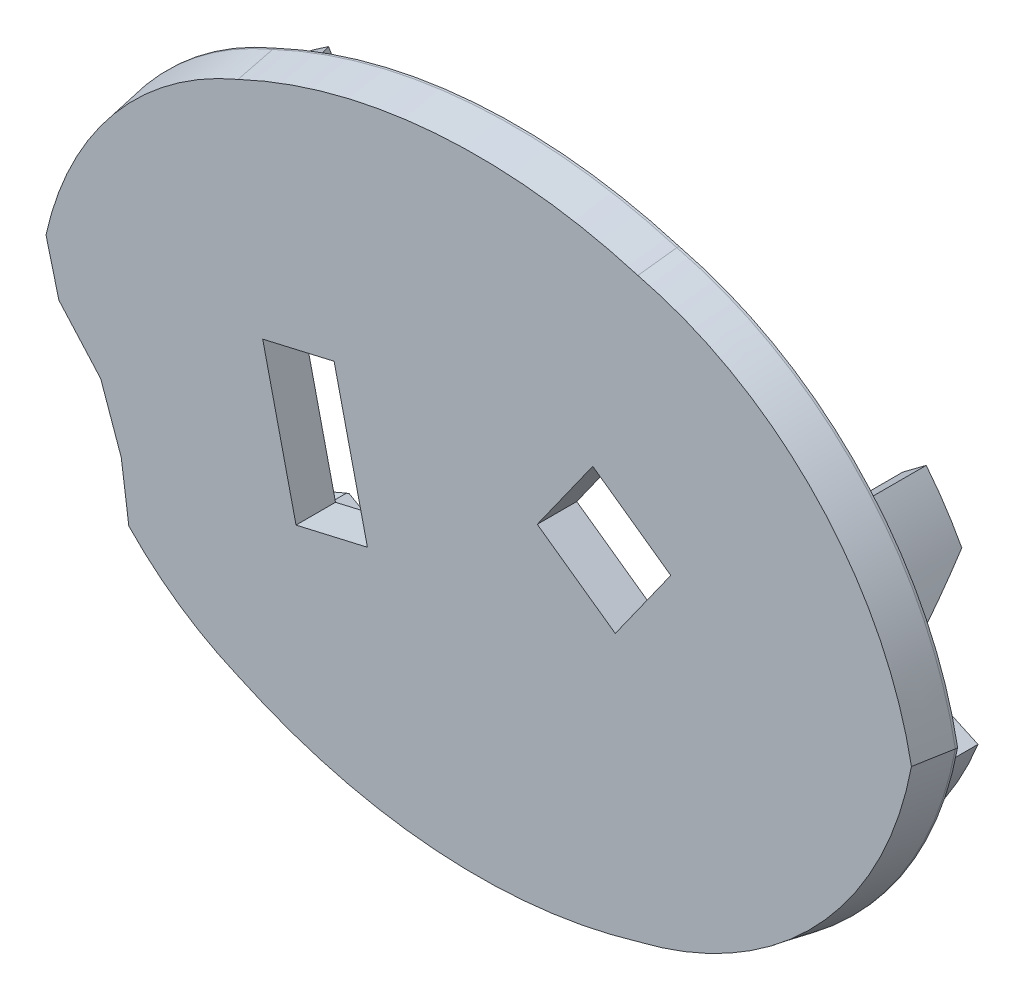
SolidWorks part; units mm, degrees
ref_plane "Ön Düzlem" through (0, 0, 0) normal (0, 0, 1) x (1, 0, 0)
ref_plane "Üst Düzlem" through (0, 0, 0) normal (0, 1, 0) x (1, 0, 0)
ref_plane "Sağ Düzlem" through (0, 0, 0) normal (1, 0, 0) x (0, 0, -1)
sketch "Çizim1" plane through (0, 0, 0) normal (0, 0, 1) x (1, 0, 0)
  line L2 (-58.677, -17.6893) -> (-56.8396, -24.8216)
  line L3 (-56.8396, -24.8216) -> (-51.1973, -31.1692)
  line L8 (-51.1973, -31.1692) -> (-48.5261, -38.7135)
  line L9 (-48.5261, -38.7135) -> (-47.4867, -46.3583)
  arc A1 (59.3086, -21.378) -> (21.9184, 18.1981) centre (10.0775, -30.4393) ccw
  arc A2 (21.9184, 18.1981) -> (-32.3459, 14.1122) centre (0.1322, -54.8435) ccw
  arc A5 (-32.3459, 14.1122) -> (-58.677, -17.6893) centre (-14.9778, -27.0699) ccw
  arc A6 (-32.3459, -56.8682) -> (-47.4867, -46.3583) centre (-14.9778, -15.6861) cw
  arc A9 (21.9184, -60.9541) -> (-32.3459, -56.8682) centre (0.1322, 12.0875) cw
  arc A10 (59.3086, -21.378) -> (21.9184, -60.9541) centre (10.0775, -12.3167) cw
extrude "Yükseklik-Ekstrüzyon1" add sketch "Çizim1" along normal blind 5.3
chamfer "Pah1" distance 5 angle 10 10 edges at (46.4645, 3.9379, 5.3) (46.4645, -46.6939, 5.3) (-5.5908, -63.9188, 5.3) (-40.464, -52.4022, 5.3) (-48.0064, -42.5359, 5.3) (-49.8617, -34.9414, 5.3) (-54.0184, -27.9954, 5.3) (-57.7583, -21.2554, 5.3) (-49.4036, 1.4341, 5.3) (-5.5908, 21.1628, 5.3) first distance on face at (43.539, 1.174, 2.65) first distance on face at (43.539, -43.93, 2.65) first distance on face at (-5.4023, -61.415, 2.65) first distance on face at (-40.1901, -52.0077, 2.65) first distance on face at (-48.0064, -42.5359, 2.65) first distance on face at (-49.8617, -34.9414, 2.65) first distance on face at (-54.0184, -27.9954, 2.65) first distance on face at (-57.7583, -21.2554, 2.65) first distance on face at (-47.4575, -0.1772, 2.65) first distance on face at (-5.4023, 18.659, 2.65)
sketch "Çizim2" plane through (0, 0, 0) normal (0, 0, -1) x (-1, 0, 0)
  line L0 (31.2763, 9.847) -> (27.7371, 3.911)
  line L1 (42.8096, -9.0722) -> (46.8763, -3.3933)
  line L2 (26.6903, -46.7388) -> (31.033, -53.1744)
  line L3 (39.0108, -42.3852) -> (40.3977, -36.6901)
  line L4 (40.3977, -36.6901) -> (43.5033, -30.0469)
  line L5 (43.5033, -30.0469) -> (48.6913, -24.7392)
  line L6 (48.6913, -24.7392) -> (53.3702, -18.2488)
  line L7 (-19.9716, 14.4087) -> (-19.195, 12.4343)
  line L8 (-41.465, -3.5137) -> (-44.5942, -1.1798)
  line L9 (-44.8646, -27.0758) -> (-51.5468, -30.1376)
  line L10 (-32.8861, -43.1983) -> (-38.7588, -48.0169)
  line L11 (-44.8646, -9.307) -> (-41.465, -3.5137)
  line L17 (39.0108, -42.3852) -> (33.018, -43.1064)
  line L18 (33.018, -43.1064) -> (26.6903, -46.7388)
  line L25 (43.1871, -44.3376) -> (39.0108, -42.3852)
  line L27 (-49.8231, -14.3904) -> (-51.9148, -14.0339)
  line L29 (-41.465, -3.5137) -> (-44.8646, -9.307)
  line L30 (9.7339, 13.9491) -> (10.6003, 16.4649)
  line L31 (-4.7237, 14.7755) -> (-4.8826, 17.1405)
  line L32 (-32.8861, -43.1983) -> (-31.6707, -49.9851)
  line L33 (-44.8646, -9.307) -> (-49.8231, -14.3904)
  line L34 (44.1329, -37.3808) -> (43.1871, -44.3376)
  line L35 (46.5637, -30.5155) -> (44.1329, -37.3808)
  line L36 (51.6981, -24.7392) -> (46.5637, -30.5155)
  line L37 (53.3702, -18.2488) -> (51.6981, -24.7392)
  line L38 (-31.6707, -49.9851) -> (-24.6864, -53.5082)
  line L39 (-24.6864, -53.5082) -> (-25.5321, -55.8827)
  arc A0 (27.7371, 3.911) -> (42.8096, -9.0722) centre (19.0626, -21.4001) cw
  arc A1 (-4.7237, 14.7755) -> (9.7339, 13.9491) centre (-0.0333, -30.0469) cw
  arc A2 (-44.8646, -27.0758) -> (-32.8861, -43.1983) centre (-10.3568, -13.9486) ccw
  arc A3 (-19.195, 12.4343) -> (-43.0296, -2.3468) centre (-9.4062, -29.9574) ccw
  arc A16 (-51.5468, -30.1376) -> (-25.5321, -55.8827) centre (-9.1964, -13.3597) ccw
  arc A17 (31.033, -53.1744) -> (43.1871, -44.3376) centre (13.6039, -16.4259) ccw
  arc A19 (46.8763, -3.3933) -> (31.2763, 9.847) centre (13.6039, -26.7852) ccw
  arc A20 (10.6003, 16.4649) -> (-4.8826, 17.1405) centre (-0.1461, -52.0591) ccw
  arc A21 (-19.9716, 14.4087) -> (-51.9148, -14.0339) centre (-9.1964, -29.8513) ccw
extrude "Yükseklik-Ekstrüzyon2" add sketch "Çizim2" along normal blind 10.5 contours L1 A19 L0 A0 | L8 A21 L27 L33 L11 | L9 A16 L10 A2 | L2 A17 L25 L17 L18 region at (-37.7924, 1.217, 0) region at (-34.4304, -46.9883, 0) region at (46.6249, -7.7509, 0) region at (42.7824, -37.6935, 0)
ref_plane "Düzlem1" through (0, 0, -2.5) normal (0, 0, -1) x (-1, 0, 0)
sketch "Çizim4" plane through (0, 0, -2.5) normal (0, 0, -1) x (-1, 0, 0)
  line L0 (-32.8861, -43.1983) -> (-38.7588, -48.0169) construction
  line L1 (-19.9716, 14.4087) -> (-19.195, 12.4343) construction
  line L2 (-49.8231, -14.3904) -> (-51.9148, -14.0339) construction
  line L3 (-44.8646, -9.307) -> (-49.8231, -14.3904) construction
  line L4 (-44.8646, -9.307) -> (-41.465, -3.5137) construction
  line L5 (-41.465, -3.5137) -> (-44.8646, -9.307) construction
  line L6 (-41.465, -3.5137) -> (-44.5942, -1.1798) construction
  line L7 (43.1871, -44.3376) -> (39.0108, -42.3852) construction
  line L8 (31.2763, 9.847) -> (27.7371, 3.911) construction
  line L9 (42.8096, -9.0722) -> (46.8763, -3.3933) construction
  line L10 (39.0108, -42.3852) -> (40.3977, -36.6901) construction
  line L11 (40.3977, -36.6901) -> (43.5033, -30.0469) construction
  line L12 (43.5033, -30.0469) -> (48.6913, -24.7392) construction
  line L13 (48.6913, -24.7392) -> (53.3702, -18.2488) construction
  line L14 (53.3702, -18.2488) -> (51.6981, -24.7392) construction
  line L15 (51.6981, -24.7392) -> (46.5637, -30.5155) construction
  line L16 (46.5637, -30.5155) -> (44.1329, -37.3808) construction
  line L17 (44.1329, -37.3808) -> (43.1871, -44.3376) construction
  line L18 (26.6903, -46.7388) -> (31.033, -53.1744) construction
  line L19 (33.018, -43.1064) -> (26.6903, -46.7388) construction
  line L20 (39.0108, -42.3852) -> (33.018, -43.1064) construction
  line L21 (9.7339, 13.9491) -> (10.6003, 16.4649) construction
  line L22 (-4.7237, 14.7755) -> (-4.8826, 17.1405) construction
  line L23 (-32.8861, -43.1983) -> (-31.6707, -49.9851) construction
  line L24 (-31.6707, -49.9851) -> (-24.6864, -53.5082) construction
  line L25 (-24.6864, -53.5082) -> (-25.5321, -55.8827) construction
  line L26 (-44.8646, -27.0758) -> (-51.5468, -30.1376) construction
  line L27 (-32.8861, -43.1983) -> (-38.7588, -48.0169)
  line L28 (-19.9716, 14.4087) -> (-19.195, 12.4343)
  line L29 (-49.8231, -14.3904) -> (-51.9148, -14.0339)
  line L30 (-44.8646, -9.307) -> (-49.8231, -14.3904)
  line L31 (-44.8646, -9.307) -> (-41.465, -3.5137)
  line L32 (-41.465, -3.5137) -> (-44.8646, -9.307)
  line L33 (-41.465, -3.5137) -> (-44.5942, -1.1798)
  line L34 (43.1871, -44.3376) -> (39.0108, -42.3852)
  line L35 (31.2763, 9.847) -> (27.7371, 3.911)
  line L36 (42.8096, -9.0722) -> (46.8763, -3.3933)
  line L37 (39.0108, -42.3852) -> (40.3977, -36.6901)
  line L38 (40.3977, -36.6901) -> (43.5033, -30.0469)
  line L39 (43.5033, -30.0469) -> (48.6913, -24.7392)
  line L40 (48.6913, -24.7392) -> (53.3702, -18.2488)
  line L41 (53.3702, -18.2488) -> (51.6981, -24.7392)
  line L42 (51.6981, -24.7392) -> (46.5637, -30.5155)
  line L43 (46.5637, -30.5155) -> (44.1329, -37.3808)
  line L44 (44.1329, -37.3808) -> (43.1871, -44.3376)
  line L45 (26.6903, -46.7388) -> (31.033, -53.1744)
  line L46 (33.018, -43.1064) -> (26.6903, -46.7388)
  line L47 (39.0108, -42.3852) -> (33.018, -43.1064)
  line L48 (9.7339, 13.9491) -> (10.6003, 16.4649)
  line L49 (-4.7237, 14.7755) -> (-4.8826, 17.1405)
  line L50 (-32.8861, -43.1983) -> (-31.6707, -49.9851)
  line L51 (-31.6707, -49.9851) -> (-24.6864, -53.5082)
  line L52 (-24.6864, -53.5082) -> (-25.5321, -55.8827)
  line L53 (-44.8646, -27.0758) -> (-51.5468, -30.1376)
  arc A0 (-19.195, 12.4343) -> (-43.0296, -2.3468) centre (-9.4062, -29.9574) ccw construction
  arc A1 (-19.9716, 14.4087) -> (-51.9148, -14.0339) centre (-9.1964, -29.8513) ccw construction
  arc A2 (42.8096, -9.0722) -> (27.7371, 3.911) centre (19.0626, -21.4001) ccw construction
  arc A3 (46.8763, -3.3933) -> (31.2763, 9.847) centre (13.6039, -26.7852) ccw construction
  arc A4 (31.033, -53.1744) -> (43.1871, -44.3376) centre (13.6039, -16.4259) ccw construction
  arc A5 (10.6003, 16.4649) -> (-4.8826, 17.1405) centre (-0.1461, -52.0591) ccw construction
  arc A6 (9.7339, 13.9491) -> (-4.7237, 14.7755) centre (-0.0333, -30.0469) ccw construction
  arc A7 (-51.5468, -30.1376) -> (-25.5321, -55.8827) centre (-9.1964, -13.3597) ccw construction
  arc A8 (-44.8646, -27.0758) -> (-32.8861, -43.1983) centre (-10.3568, -13.9486) ccw construction
  arc A9 (-19.195, 12.4343) -> (-43.0296, -2.3468) centre (-9.4062, -29.9574) ccw
  arc A10 (-19.9716, 14.4087) -> (-51.9148, -14.0339) centre (-9.1964, -29.8513) ccw
  arc A11 (42.8096, -9.0722) -> (27.7371, 3.911) centre (19.0626, -21.4001) ccw
  arc A12 (46.8763, -3.3933) -> (31.2763, 9.847) centre (13.6039, -26.7852) ccw
  arc A13 (31.033, -53.1744) -> (43.1871, -44.3376) centre (13.6039, -16.4259) ccw
  arc A14 (10.6003, 16.4649) -> (-4.8826, 17.1405) centre (-0.1461, -52.0591) ccw
  arc A15 (9.7339, 13.9491) -> (-4.7237, 14.7755) centre (-0.0333, -30.0469) ccw
  arc A16 (-51.5468, -30.1376) -> (-25.5321, -55.8827) centre (-9.1964, -13.3597) ccw
  arc A17 (-44.8646, -27.0758) -> (-32.8861, -43.1983) centre (-10.3568, -13.9486) ccw
extrude "Yükseklik-Ekstrüzyon3" add sketch "Çizim4" against normal up to surface (2.5 mm away) contours L28 A10 L33 A9 | A15 L48 A14 L49 | L44 L43 L42 L41 L40 L39 L38 L37 L34 | L27 A16 L52 L51 L50 region at (32.2105, -49.952, -2.5) region at (32.3825, 7.2589, -2.5) region at (-44.8221, -33.1734, -2.5) region at (-2.8392, 15.9234, -2.5) up to face at (46.6374, -8.4252, 0)
chamfer "Pah4" distance 6 angle 55 1 edges at (50.869, -14.2121, -10.5) first distance on face at (46.6374, -8.4252, -10.5)
chamfer "Pah5" distance 6 angle 53 1 edges at (35.8224, -45.6076, -10.5) first distance on face at (42.5671, -37.5104, -10.5)
chamfer "Pah8" distance 5 angle 60 1 edges at (-29.5067, 6.879, -10.5) first distance on face at (-37.6992, 0.9356, -10.5)
sketch "Çizim5" plane through (0, 0, -10.5) normal (0, 0, -1) x (-1, 0, 0)
  line L0 (43.1871, -44.3376) -> (39.4463, -40.5968)
  line L1 (39.0108, -42.3852) -> (39.4463, -40.5968)
  line L3 (39.0108, -42.3852) -> (43.1871, -44.3376)
extrude "Yükseklik-Ekstrüzyon4" add sketch "Çizim5" against normal blind 10.5
chamfer "Pah10" distance 6.5 angle 50 1 edges at (-41.3167, -42.4672, -10.5) first distance on face at (-35.4662, -45.1509, -10.5)
sketch "Çizim6" plane through (0, 0, 0) normal (0, 0, -1) x (-1, 0, 0)
  line L0 (-26.105, -15.3171) -> (-15.6301, -7.8656)
  line L1 (24.2046, -34.6186) -> (28.68, -15.2336)
  line L2 (24.2046, -34.6186) -> (14.6201, -32.4059)
  line L3 (14.6201, -32.4059) -> (19.0955, -13.0208)
  line L4 (28.68, -15.2336) -> (19.0955, -13.0208)
  line L5 (-15.6301, -7.8656) -> (-8.1786, -18.3405)
  line L6 (-8.1786, -18.3405) -> (-18.6535, -25.7921)
  line L7 (-18.6535, -25.7921) -> (-26.105, -15.3171)
extrude "Kes-Ekstrüzyon1" cut sketch "Çizim6" against normal blind 10.5
